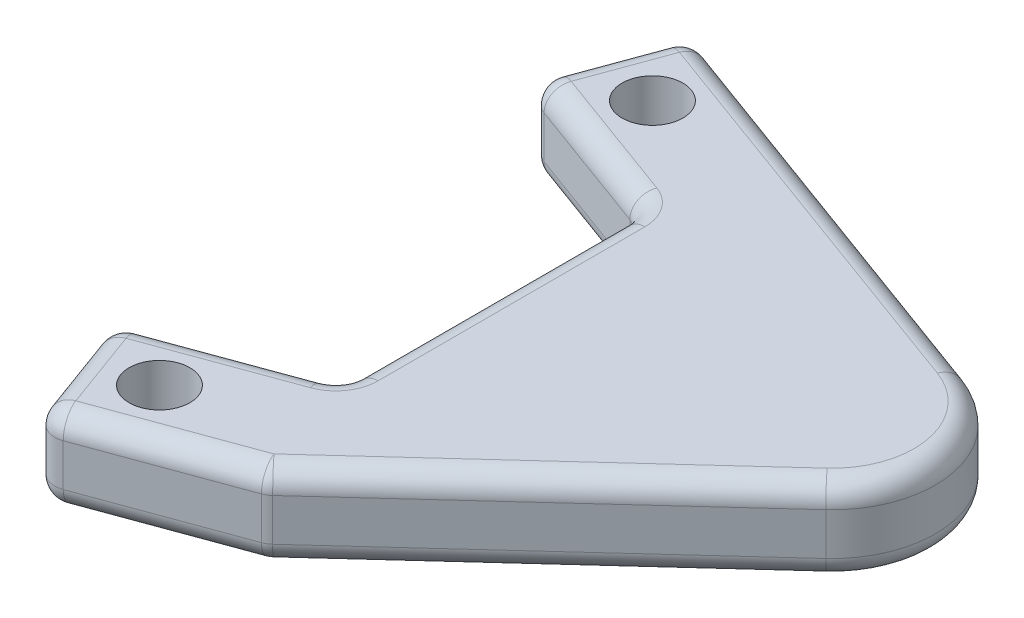
SolidWorks part; units mm, degrees
ref_plane "Front Plane" through (0, 0, 0) normal (0, 0, 1) x (1, 0, 0)
ref_plane "Top Plane" through (0, 0, 0) normal (0, 1, 0) x (1, 0, 0)
ref_plane "Right Plane" through (0, 0, 0) normal (1, 0, 0) x (0, 0, -1)
sketch "Sketch1" plane through (0, 0, 0) normal (0, 1, 0) x (1, 0, 0)
  line L0 (21.2293, -21.8246) -> (53.3227, -33.5685)
  line L7 (30.6561, -57.7105) -> (30.6561, -35.4168)
  line L8 (30.6561, -35.4168) -> (17.9561, -30.7695)
  line L9 (17.9561, -30.7695) -> (21.2293, -21.8246)
  line L11 (21.2293, -71.3027) -> (33.9293, -66.6554)
  line L12 (33.9293, -66.6554) -> (55.8907, -46.5691)
  line L13 (30.6561, -57.7105) -> (17.9561, -62.3578)
  line L14 (-48.9224, -86.8307) -> (30.1351, -57.9011) construction
  line L15 (17.9561, -62.3578) -> (21.2293, -71.3027)
  line L16 (50.6586, -60.5337) -> (-49.8568, -97.3153) construction
  line L25 (30.6561, -57.1557) -> (30.6561, -35.9716) construction
  line L26 (30.1351, -35.2262) -> (-48.9224, -6.2966) construction
  line L29 (-49.8568, 4.188) -> (29.5896, -24.8839) construction
  arc A0 (55.8907, -46.5691) -> (53.3227, -33.5685) centre (50.6586, -40.8487) ccw
  dimension "D1" = 12.7
  dimension "D3" = 12.7
extrude "Boss-Extrude1" add sketch "Sketch1" along normal blind 6.35
sketch "Sketch2" plane through (0, 6.35, 0) normal (0, 1, 0) x (1, 0, 0)
  line L0 (30.6561, -35.4168) -> (30.6561, -57.7105) construction
  line L1 (21.2293, -71.3027) -> (33.9293, -66.6554) construction
  line L2 (24.3061, -65.1055) -> (25.9427, -69.578) construction
  line L4 (24.3061, -65.1055) -> (22.6695, -60.633) construction
  line L5 (30.6561, -57.7105) -> (17.9561, -62.3578) construction
  line L6 (24.3061, -28.0218) -> (22.6695, -32.4943) construction
  line L7 (17.9561, -30.7695) -> (30.6561, -35.4168) construction
  line L8 (24.3061, -28.0218) -> (25.9427, -23.5494) construction
  line L9 (53.3227, -33.5685) -> (21.2293, -21.8246) construction
  line L10 (53.3227, -33.5685) -> (21.2293, -21.8246) construction
  circle A10 centre (24.3061, -65.1055) radius 2.286
  circle A11 centre (24.3061, -28.0218) radius 2.286
  dimension "D1" = 6.35
  dimension "D4" = 4.572
  dimension "D2" = 6.35
extrude "Cut-Extrude1" cut sketch "Sketch2" against normal through all
sketch "Sketch5" plane through (0, 0, 0) normal (0, -1, 0) x (1, 0, 0)
  line L0 (50.6586, 40.8432) -> (57.8976, 40.8432) construction
  line L1 (50.6586, 48.0877) -> (50.6586, 40.8432) construction
  circle A0 centre (50.6586, 40.8432) radius 2.286
  circle A1 centre (50.6586, 40.8487) radius 7.239 construction
  dimension "D1" = 4.572
extrude "Cut-Extrude2" cut sketch "Sketch5" against normal offset from surface (4.7625 mm away) 1.5875 contours A0 up to face at (24.3061, 6.35, 67.3915)
fillet "Fillet1" radius 1.5875 25 edges at (24.3061, 6.35, 33.0932) (24.3061, 0, 33.0932) (24.3061, 6.35, 60.0341) (24.3061, 0, 60.0341) (37.276, 6.35, 27.6965) (58.2639, 6.35, 39.3464) (37.276, 0, 27.6965) (58.2639, 0, 39.3464) (30.6561, 3.175, 35.4168) (30.6561, 6.35, 46.5637) (30.6561, 3.175, 57.7105) (30.6561, 0, 46.5637) (21.2293, 3.175, 21.8246) (19.5927, 6.35, 26.297) (17.9561, 3.175, 30.7695) (19.5927, 0, 26.297) (44.91, 6.35, 56.6123) (44.91, 0, 56.6123) (27.5793, 6.35, 68.9791) (33.9293, 3.175, 66.6554) (27.5793, 0, 68.9791) (17.9561, 3.175, 62.3578) (19.5927, 6.35, 66.8303) (21.2293, 3.175, 71.3027) (19.5927, 0, 66.8303)
